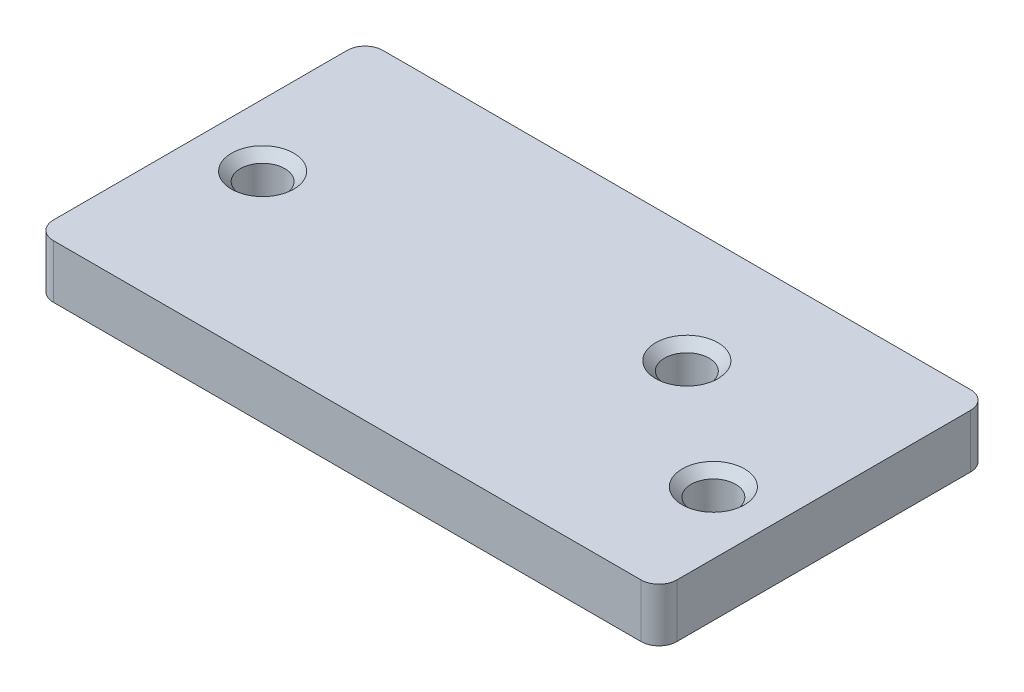
SolidWorks part; units mm, degrees
material "PLA"
ref_plane "Front Plane" through (0, 0, 0) normal (0, 0, 1) x (1, 0, 0)
ref_plane "Top Plane" through (0, 0, 0) normal (0, 1, 0) x (1, 0, 0)
ref_plane "Right Plane" through (0, 0, 0) normal (1, 0, 0) x (0, 0, -1)
sketch "Sketch3" plane through (0, 0, 0) normal (0, 1, 0) x (1, 0, 0)
  line L1 (-35, -18.5) -> (35, -18.5)
  line L2 (-35, -18.5) -> (-35, 18.5)
  line L3 (-35, 18.5) -> (35, 18.5)
  line L4 (35, -18.5) -> (35, 18.5)
  line L5 (-35, -18.5) -> (35, 18.5) construction
  line L6 (-35, 18.5) -> (35, -18.5) construction
  point P0 (0, 0)
  dimension "D1" = 37
  dimension "D2" = 70
extrude "Boss-Extrude1" add sketch "Sketch3" along normal blind 6 contours L1 L4 L3 L2
fillet "Fillet1" radius 2 4 edges at (35, 3, 18.5) (-35, 3, -18.5) (-35, 3, 18.5) (35, 3, -18.5)
sketch "Sketch4" plane through (0, 6, 0) normal (0, 1, 0) x (1, 0, 0)
  line L1 (-33, -18.5) -> (33, -18.5) construction
  circle A0 centre (-28, 0) radius 2.5
  circle A1 centre (14.24, 5.39) radius 2.5
  circle A2 centre (28, -5.39) radius 2.5
  dimension "D2" = 5
  dimension "D3" = 5
  dimension "D4" = 5
  dimension "D1" = 42.24
  dimension "D5" = 13.76
  dimension "D6" = 28
  dimension "D7" = 10.78
  dimension "D8" = 13.11
extrude "Cut-Extrude1" cut sketch "Sketch4" against normal blind 5 contours A2
extrude "Cut-Extrude2" cut sketch "Sketch4<3>" against normal blind 5 contours A1
sketch "Sketch4<3>" plane through (0, 6, 0) normal (0, 1, 0) x (1, 0, 0) same geometry as "Sketch4"
extrude "Cut-Extrude3" cut sketch "Sketch4<5>" against normal blind 5 contours A0
sketch "Sketch4<5>" plane through (0, 6, 0) normal (0, 1, 0) x (1, 0, 0) same geometry as "Sketch4"
chamfer "Chamfer1" distance 1 angle 45 3 edges at (14.24, 6, -2.89) (-28, 6, 2.5) (28, 6, 7.89)
